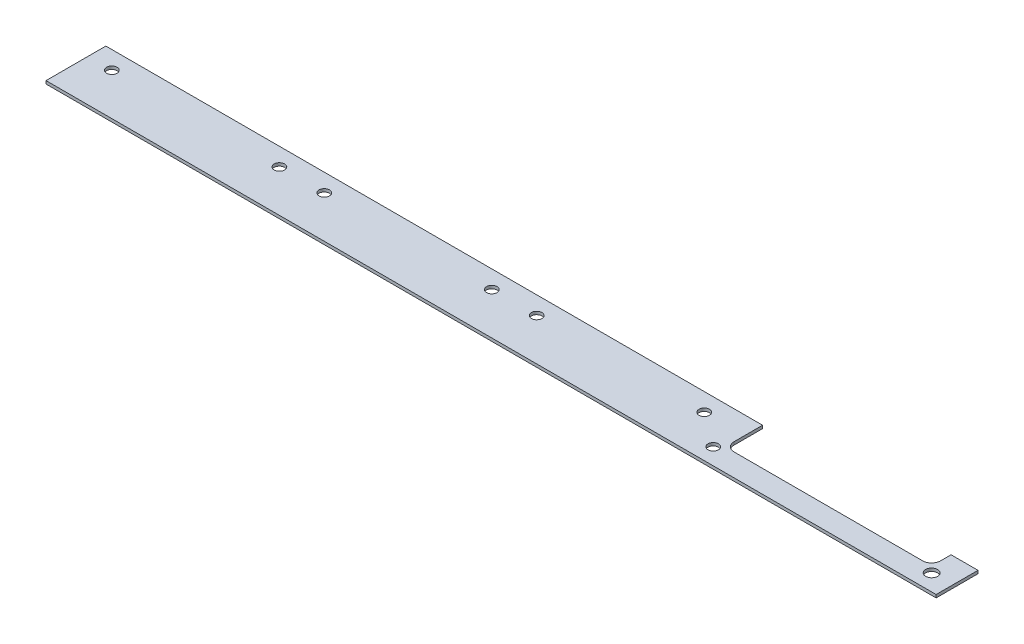
SolidWorks part; units mm, degrees
material "Простая углеродистая сталь"
ref_plane "Спереди" through (0, 0, 0) normal (0, 0, 1) x (1, 0, 0)
ref_plane "Сверху" through (0, 0, 0) normal (0, 1, 0) x (1, 0, 0)
ref_plane "Справа" through (0, 0, 0) normal (1, 0, 0) x (0, 0, -1)
sketch "Эскиз1" plane through (0, 0, 0) normal (0, 1, 0) x (1, 0, 0)
  line L0 (219.5, 20) -> (219.5, 10.5)
  line L1 (0, 0) -> (297.5, 0)
  line L2 (0, 0) -> (0, 20)
  line L3 (0, 20) -> (219.5, 20)
  line L5 (222.5, 7.5) -> (285.5, 7.5)
  line L7 (288.5, 10.5) -> (288.5, 14)
  line L8 (288.5, 14) -> (297.5, 14)
  line L9 (297.5, 14) -> (297.5, 0)
  circle A1 centre (217.5, 5.5) radius 1.75
  circle A2 centre (64, 14) radius 1.75
  circle A3 centre (8, 14) radius 1.75
  circle A4 centre (79, 14) radius 1.75
  circle A5 centre (135, 14) radius 1.75
  circle A8 centre (290.5, 5.5) radius 2
  arc A9 (219.5, 10.5) -> (222.5, 7.5) centre (222.5, 10.5) ccw
  arc A10 (285.5, 7.5) -> (288.5, 10.5) centre (285.5, 10.5) ccw
  circle A11 centre (150, 14) radius 1.75
  circle A12 centre (206, 14) radius 1.75
  dimension "D2" = 3
  dimension "D3" = 3
  dimension "D1" = 3
extrude "Бобышка-Вытянуть1" add sketch "Эскиз1" along normal blind 1
